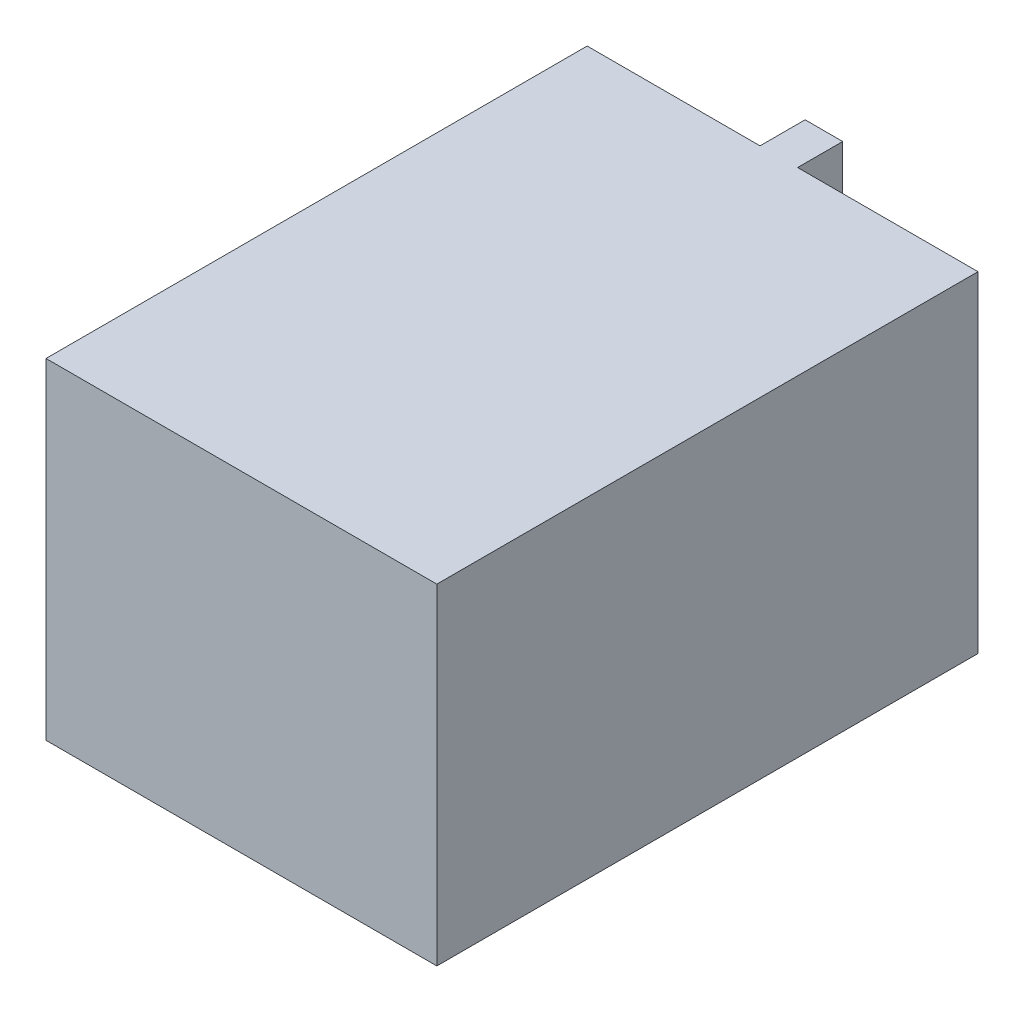
SolidWorks part; units mm, degrees
material "6061 Alloy"
ref_plane "Front Plane" through (0, 0, 0) normal (0, 0, 1) x (1, 0, 0)
ref_plane "Top Plane" through (0, 0, 0) normal (0, 1, 0) x (1, 0, 0)
ref_plane "Right Plane" through (0, 0, 0) normal (1, 0, 0) x (0, 0, -1)
sketch "Sketch1" plane through (0, 0, 0) normal (0, 1, 0) x (1, 0, 0)
  line L0 (-19.05, -228.6) -> (19.05, -228.6) construction
  line L1 (165.1, 228.6) -> (-165.1, 228.6) construction
  line L2 (165.1, 228.6) -> (165.1, -228.6)
  line L3 (165.1, -228.6) -> (-165.1, -228.6) construction
  line L4 (-165.1, 228.6) -> (-165.1, -228.6)
  line L5 (165.1, 228.6) -> (-165.1, -228.6) construction
  line L6 (165.1, -228.6) -> (-165.1, 228.6) construction
  line L7 (-19.05, -228.6) -> (-19.05, -269.875) construction
  line L8 (19.05, -228.6) -> (19.05, -269.875) construction
  line L9 (-19.05, -269.875) -> (19.05, -269.875) construction
  line L10 (-165.1, -228.6) -> (-19.05, -228.6)
  line L11 (19.05, -228.6) -> (-19.05, -228.6)
  line L12 (12.7, 228.6) -> (-19.05, 228.6) construction
  line L13 (12.7, 228.6) -> (12.7, 266.7)
  line L14 (19.05, -228.6) -> (165.1, -228.6)
  line L15 (-19.05, 228.6) -> (-19.05, 266.7)
  line L16 (12.7, 266.7) -> (-19.05, 266.7)
  line L17 (-19.05, 228.6) -> (-165.1, 228.6)
  line L18 (12.7, 228.6) -> (165.1, 228.6)
  point P0 (0, 0)
  point P13 (-3.175, 228.6)
  dimension "D1" = 330.2
  dimension "D2" = 457.2
  dimension "D3" = 146.05
  dimension "D4" = 146.05
  dimension "D5" = 41.275
  dimension "D6" = 146.05
  dimension "D7" = 31.75
  dimension "D8" = 38.1
extrude "Boss-Extrude1" add sketch "Sketch1" along normal blind 279.4
